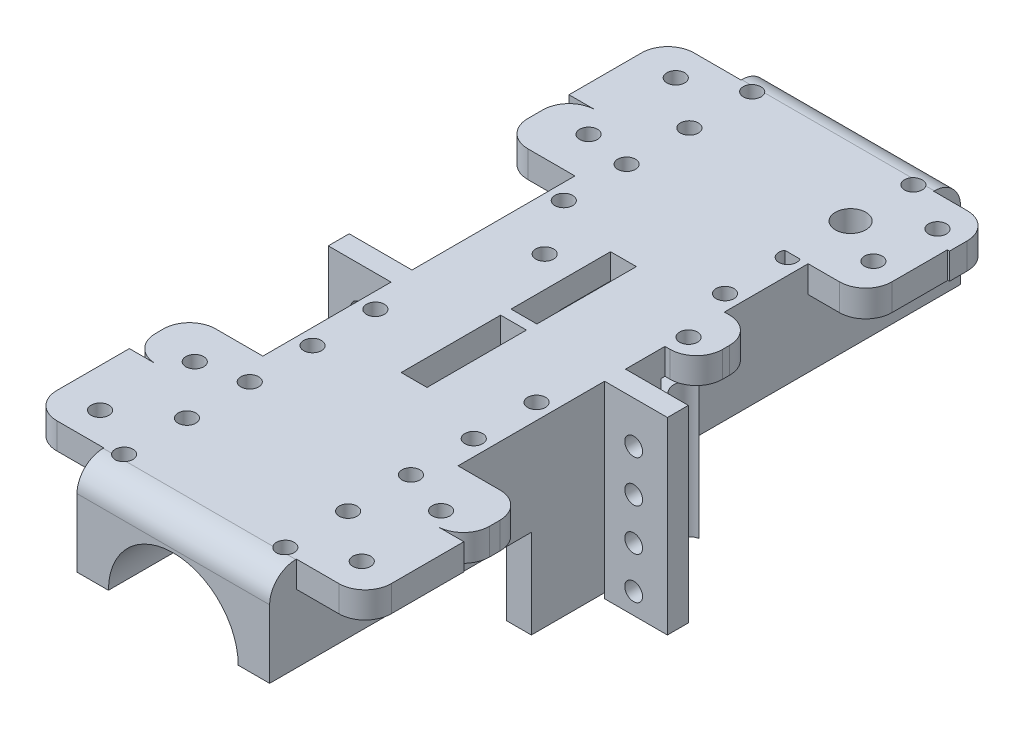
SolidWorks part; units mm, degrees
ref_plane "Plan de face" through (0, 0, 0) normal (0, 0, 1) x (1, 0, 0)
ref_plane "Plan de dessus" through (0, 0, 0) normal (0, 1, 0) x (1, 0, 0)
ref_plane "Plan de droite" through (0, 0, 0) normal (1, 0, 0) x (0, 0, -1)
sketch "Esquisse1" plane through (0, 0, 0) normal (0, 0, 1) x (1, 0, 0)
  line L0 (0, 0) -> (-84.6745, 0) construction
  line L1 (0, 0) -> (94.0931, 0) construction
  line L2 (-12.4, 0) -> (-18.4, 0)
  line L3 (0, 0) -> (0, 12.4) construction
  line L4 (-18.4, 0) -> (-18.4, 18)
  line L5 (-18.4, 18) -> (18.4, 18)
  line L6 (18.4, 0) -> (18.4, 18)
  line L7 (12.4, 0) -> (18.4, 0)
  line L8 (0, 12.4) -> (0, 18) construction
  arc A0 (-12.4, 0) -> (12.4, 0) centre (0, 0) cw
  point P11 (0, 18)
  dimension "D1" = 6
  dimension "D2" = 18
extrude "Boss.-Extru.1" add sketch "Esquisse1" along normal blind 132
sketch "Esquisse3" plane through (0, 18, 0) normal (0, -1, 0) x (1, 0, 0)
  line L0 (-18.4, 66) -> (18.4, 66) construction
  line L3 (0, 66) -> (0, 73.4675) construction
  line L4 (-18.4, 132) -> (-18.4, 0) construction
  line L5 (2.4701, 46) -> (-2.4701, 46)
  line L6 (2.4701, 46) -> (2.4701, 86)
  line L7 (2.4701, 86) -> (-2.4701, 86)
  line L8 (-2.4701, 46) -> (-2.4701, 86)
  line L9 (2.4701, 46) -> (-2.4701, 86) construction
  line L10 (2.4701, 86) -> (-2.4701, 46) construction
  dimension "D1" = 40
extrude "Enlèv. mat.-Extru.2" cut sketch "Esquisse3" along normal blind 9
sketch "Esquisse4" plane through (0, 18, 0) normal (0, 1, 0) x (1, 0, 0)
  line L0 (18.4, -12) -> (-19.7679, -12) construction
  line L1 (0, 0) -> (0, -28.5028) construction
  line L2 (15.4, 0) -> (15.4, -28.5028) construction
  line L3 (18.4, -6) -> (-18.4211, -6) construction
  line L4 (18.4, 0) -> (-18.4, 0) construction
  line L5 (18.4, -132) -> (18.4, 0) construction
  line L6 (18.4, -66) -> (-18.4, -66) construction
  line L7 (-18.4, -132) -> (-18.4, 0) construction
  circle A0 centre (15.4, -6) radius 1.7
  circle A1 centre (15.4, -18) radius 1.7
  circle A2 centre (-15.4, -6) radius 1.7
  circle A3 centre (-15.4, -18) radius 1.7
  circle A4 centre (15.4, -30) radius 1.7
  circle A5 centre (-15.4, -30) radius 1.7
  circle A6 centre (15.4, -42) radius 1.7
  circle A7 centre (-15.4, -42) radius 1.7
  circle A10 centre (-15.4, -126) radius 1.7
  circle A11 centre (-15.4, -114) radius 1.7
  circle A12 centre (-15.4, -102) radius 1.7
  circle A13 centre (-15.4, -90) radius 1.7
  circle A14 centre (-15.4, -78) radius 1.7
  circle A15 centre (15.4, -78) radius 1.7
  circle A16 centre (15.4, -90) radius 1.7
  circle A17 centre (15.4, -102) radius 1.7
  circle A18 centre (15.4, -114) radius 1.7
  circle A19 centre (15.4, -126) radius 1.7
  circle A20 centre (15.4, -54) radius 1.7 [skipped]
  circle A21 centre (-15.4, -54) radius 1.7 [skipped]
  dimension "D1" = 3
  dimension "D2" = 6
  dimension "D3" = 6
  dimension "D4" = 5
extrude "Enlèv. mat.-Extru.3" cut sketch "Esquisse4" against normal blind 18
sketch "Esquisse5" plane through (0, 18, 0) normal (0, 1, 0) x (1, 0, 0)
  line L0 (0, 0) -> (0, -132) construction
  line L1 (18.4, 0) -> (12.4, 0)
  line L2 (18.4, 0) -> (18.4, -24)
  line L3 (18.4, -24) -> (12.4, -24)
  line L4 (12.4, 0) -> (12.4, -24)
  line L5 (18.4, 0) -> (-18.4, 0) construction
  line L6 (18.4, -132) -> (-18.4, -132) construction
  line L7 (18.4, -66) -> (-18.4, -66) construction
  line L8 (18.4, -132) -> (18.4, 0) construction
  line L9 (-18.4, -132) -> (-18.4, 0) construction
  line L10 (-18.4, -132) -> (-12.4, -132)
  line L11 (-12.4, -132) -> (-12.4, -108)
  line L12 (-18.4, -108) -> (-12.4, -108)
  line L13 (-18.4, -132) -> (-18.4, -108)
  line L14 (-18.4, 0) -> (-18.4, -24)
  line L15 (-18.4, -24) -> (-12.4, -24)
  line L16 (-12.4, 0) -> (-12.4, -24)
  line L17 (-18.4, 0) -> (-12.4, 0)
  line L18 (12.4, -132) -> (12.4, -108)
  line L19 (18.4, -108) -> (12.4, -108)
  line L20 (18.4, -132) -> (18.4, -108)
  line L21 (18.4, -132) -> (12.4, -132)
  dimension "D1" = 24
  dimension "D2" = 6
sketch "Esquisse7" plane through (-18.4, 0, 0) normal (-1, 0, 0) x (0, 0, 1)
  line L0 (66, 18) -> (66, 0) construction
  line L1 (132, 18) -> (0, 18) construction
  line L2 (132, 0) -> (0, 0) construction
  line L4 (65, 0) -> (67, 0)
  line L5 (65, 0) -> (65, 18)
  line L6 (65, 18) -> (67, 18)
  line L7 (67, 0) -> (67, 18)
  line L8 (65, 0) -> (67, 18) construction
  line L9 (65, 18) -> (67, 0) construction
  point P6 (66, 9)
  dimension "D1" = 2
extrude "Boss.-Extru.2" add sketch "Esquisse7" against normal through all
sketch "Esquisse8" plane through (0, 0, 65) normal (0, 0, -1) x (-1, 0, 0)
  line L0 (0, 0) -> (16.5032, 0) construction
  line L1 (-12.4, 0) -> (12.4, 0) construction
  line L2 (0, 0) -> (-16.5316, 0) construction
  line L3 (12.775, 0) -> (-12.775, 0)
  arc A0 (12.775, 0) -> (-12.775, 0) centre (0, 0) ccw
extrude "Enlèv. mat.-Extru.5" cut sketch "Esquisse8" along normal blind 15
sketch "Esquisse9" plane through (0, 0, 67) normal (0, 0, 1) x (1, 0, 0)
  line L0 (0, 0) -> (13.8492, 0) construction
  line L1 (12.4, 0) -> (-12.4, 0) construction
  line L2 (0, 0) -> (-14.6616, 0) construction
  line L3 (12.775, 0) -> (-12.775, 0)
  arc A0 (12.775, 0) -> (-12.775, 0) centre (0, 0) ccw
extrude "Enlèv. mat.-Extru.6" cut sketch "Esquisse9" along normal blind 15
sketch "Esquisse10" plane through (0, 0, 0) normal (0, -1, 0) x (1, 0, 0)
  line L0 (12.775, 82) -> (18.4, 82)
  line L1 (18.4, 132) -> (18.4, 0) construction
  line L2 (12.775, 50) -> (18.4, 50)
  line L3 (18.4, 50) -> (18.4, 82)
  line L4 (12.775, 82) -> (12.775, 50)
  line L5 (0, 67) -> (0, 64.9415) construction
  line L6 (12.775, 67) -> (-12.775, 67) construction
  line L7 (-12.775, 50) -> (-18.4, 50)
  line L8 (-18.4, 50) -> (-18.4, 82)
  line L9 (-12.775, 82) -> (-12.775, 50)
  line L10 (-12.775, 82) -> (-18.4, 82)
extrude "Boss.-Extru.3" add sketch "Esquisse10" along normal blind 17
sketch "Esquisse21" plane through (-18.4, 0, 0) normal (-1, 0, 0) x (0, 0, 1)
  line L0 (15.8275, 12.9) -> (113.6873, 12.9) construction
  line L1 (26.5684, 18) -> (120.3195, 18) construction
  line L2 (132, 18) -> (0, 18) construction
  line L3 (26.5684, 18) -> (12.3669, 18) construction
  line L5 (24, 18) -> (36.8707, 18)
  line L6 (24, 18) -> (24, 12.9)
  line L7 (24, 12.9) -> (36.8707, 12.9)
  line L8 (36.8707, 18) -> (36.8707, 12.9)
  line L9 (108, 18) -> (96.4942, 18)
  line L10 (108, 18) -> (108, 12.9)
  line L11 (108, 12.9) -> (96.4942, 12.9)
  line L12 (96.4942, 18) -> (96.4942, 12.9)
  dimension "D1" = 5.1
extrude "Boss.-Extru.7" add sketch "Esquisse21" along normal blind 14
sketch "Esquisse12" plane through (18.4, 0, 0) normal (1, 0, 0) x (0, 0, -1)
  line L1 (-108, 18) -> (-96, 18)
  line L2 (-108, 18) -> (-108, 10)
  line L3 (-108, 10) -> (-96, 10)
  line L4 (-96, 18) -> (-96, 10)
  dimension "D1" = 8
  dimension "D2" = 12
extrude "Boss.-Extru.4" add sketch "Esquisse12" along normal blind 13
sketch "Esquisse14" plane through (18.4, 0, 0) normal (1, 0, 0) x (0, 0, -1)
  line L0 (-96, 18) -> (0, 18) construction
  line L1 (-56.4694, 18) -> (-45.1194, 18)
  line L2 (-56.4694, 18) -> (-56.4694, 10.412)
  line L3 (-56.4694, 10.412) -> (-45.1194, 10.412)
  line L4 (-45.1194, 18) -> (-45.1194, 10.412)
extrude "Boss.-Extru.5" add sketch "Esquisse14" along normal blind 6
sketch "Esquisse16" plane through (24.4, 0, 0) normal (1, 0, 0) x (0, 0, -1)
  line L1 (-43.9372, 13.05) -> (-57.196, 13.05)
  line L2 (-43.9372, 13.05) -> (-43.9372, 8.7778)
  line L3 (-43.9372, 8.7778) -> (-57.196, 8.7778)
  line L4 (-57.196, 13.05) -> (-57.196, 8.7778)
extrude "Enlèv. mat.-Extru.7" cut sketch "Esquisse16" against normal blind 11
sketch "Esquisse17" plane through (18.4, 0, 0) normal (1, 0, 0) x (0, 0, -1)
  line L0 (-45.1194, 18) -> (0, 18) construction
  line L1 (-29.1148, 18) -> (-13.5015, 18)
  line L2 (-29.1148, 18) -> (-29.1148, 12.8991)
  line L3 (-29.1148, 12.8991) -> (-13.5015, 12.8991)
  line L4 (-13.5015, 18) -> (-13.5015, 12.8991)
extrude "Boss.-Extru.6" add sketch "Esquisse17" along normal blind 11 and the other way blind 11
sketch "Esquisse11" plane through (0, 18, 0) normal (0, 1, 0) x (1, 0, 0)
  line L0 (-18.4, -66.6824) -> (18.5601, -66.6824) construction
  line L2 (15.4, -6) -> (15.4, -18) construction
  line L3 (-35.4042, -116.6824) -> (36.1198, -116.6824) construction
  line L4 (-37.228, -16.6824) -> (37.9436, -16.6824) construction
  line L5 (0, -132) -> (0, 0) construction
  line L6 (26.63, -116.6824) -> (26.63, -16.6824) construction
  line L7 (-26.63, -116.6824) -> (-26.63, -16.6824) construction
  line L10 (24.22, -116.6824) -> (24.22, -16.6824) construction
  line L11 (26.63, -102.6824) -> (-26.63, -102.6824) construction
  line L12 (19.13, -116.6824) -> (19.13, -16.6824) construction
  line L13 (-26.63, -52.6824) -> (26.63, -52.6824) construction
  line L14 (26.63, -22.4624) -> (-26.63, -22.4624) construction
  line L15 (-8.37, -116.6824) -> (-8.37, -16.6824) construction
  line L16 (-23.98, -116.6824) -> (-23.98, -16.6824) construction
  line L17 (26.63, -103.9224) -> (-26.63, -103.9224) construction
  line L18 (-26.63, -28.6824) -> (26.63, -28.6824) construction
  circle A0 centre (24.22, -105.0655) radius 1.7
  circle A1 centre (19.13, -52.6824) radius 1.7
  circle A2 centre (24.22, -22.4624) radius 1.7
  circle A3 centre (-8.37, -52.6824) radius 1.7
  circle A4 centre (15.4, -6) radius 1.3
  circle A5 centre (15.4, -18) radius 2.9164
  circle A6 centre (-23.98, -103.9224) radius 1.7
  circle A7 centre (-23.98, -28.6824) radius 1.7
  dimension "D8" = 64
  dimension "D9" = 5.78
  dimension "D10" = 35
  dimension "D11" = 2.65
  dimension "D13" = 12
  dimension "D1" = 50
  dimension "D2" = 50
  dimension "D3" = 26.63
  dimension "D4" = 26.63
  dimension "D5" = 2.41
  dimension "D6" = 14
  dimension "D7" = 7.5
  dimension "D12" = 12.76
extrude "Enlèv. mat.-Extru.8" cut sketch "Esquisse11" against normal blind 8
fillet "Congé1" radius 5 9 edges at (24.4, 15.525, 45.1194) (24.4, 15.525, 56.4694) (31.4, 14, 96) (31.4, 14, 108) (29.4, 15.4496, 29.1148) (-32.4, 15.45, 108) (-32.4, 15.45, 96.4942) (-32.4, 15.45, 36.8707) (-32.4, 15.45, 24)
sketch "Esquisse18" plane through (-2.4701, 0, 0) normal (1, 0, 0) x (0, 0, -1)
  line L1 (-55.739, 13.14) -> (-46.0613, 13.14)
  line L2 (-55.739, 13.14) -> (-55.739, 4.8868)
  line L3 (-55.739, 4.8868) -> (-46.0613, 4.8868)
  line L4 (-46.0613, 13.14) -> (-46.0613, 4.8868)
extrude "Enlèv. mat.-Extru.9" cut sketch "Esquisse18" against normal blind 10
fillet "Congé2" radius 5 2 edges at (0, 18, 0) (0, 18, 132)
sketch "Esquisse19" plane through (18.4, 0, 0) normal (1, 0, 0) x (0, 0, -1)
  line L0 (-24, 12.8991) -> (-139.8858, 12.8991) construction
  line L1 (-24, 12.8991) -> (7.4507, 12.8991) construction
  line L3 (7.4507, 12.8991) -> (-132, 12.8991)
  line L4 (7.4507, 12.8991) -> (7.4507, 5.3045)
  line L5 (7.4507, 5.3045) -> (-132, 5.3045)
  line L6 (-132, 12.8991) -> (-132, 5.3045)
extrude "Enlèv. mat.-Extru.10" cut sketch "Esquisse19" along normal blind 24
sketch "Esquisse20" plane through (0, 0, 0) normal (0, -1, 0) x (1, 0, 0)
  line L0 (0, 67) -> (0, 65) construction
  line L1 (12.775, 67) -> (-12.775, 67) construction
  line L2 (12.775, 65) -> (-12.775, 65) construction
  line L4 (-13.65, 45.9837) -> (13.65, 45.9837)
  line L5 (-13.65, 45.9837) -> (-13.65, 86.0163)
  line L6 (-13.65, 86.0163) -> (13.65, 86.0163)
  line L7 (13.65, 45.9837) -> (13.65, 86.0163)
  line L8 (-13.65, 45.9837) -> (13.65, 86.0163) construction
  line L9 (-13.65, 86.0163) -> (13.65, 45.9837) construction
  point P6 (0, 66)
  dimension "D1" = 27.3
extrude "Enlèv. mat.-Extru.11" cut sketch "Esquisse20" along normal blind 22
sketch "Esquisse22" plane through (0, 13.05, 0) normal (0, -1, 0) x (1, 0, 0)
  circle A0 centre (19.13, 52.6824) radius 2.7804
extrude "Enlèv. mat.-Extru.12" cut sketch "Esquisse22" along normal blind 33
sketch "Esquisse23" plane through (0, 13.14, 0) normal (0, -1, 0) x (1, 0, 0)
  line L0 (-10.9627, 54.7361) -> (-30.5745, 60.2092)
  line L1 (-30.5745, 60.2092) -> (-30.5745, 54.652)
  line L2 (-30.5745, 54.652) -> (-10.9627, 50.3961)
  line L3 (-10.9627, 50.3961) -> (-10.9627, 54.7361)
extrude "Enlèv. mat.-Extru.13" cut sketch "Esquisse23" along normal blind 23
sketch "Esquisse29" plane through (18.4, 0, 0) normal (1, 0, 0) x (0, 0, -1)
  line L0 (-132, 0) -> (0, 0) construction
  line L1 (-96, 18) -> (-56.4694, 18) construction
  line L2 (-68, -18) -> (-64, -18)
  line L3 (-68, -18) -> (-68, 18)
  line L4 (-68, 18) -> (-64, 18)
  line L5 (-64, -18) -> (-64, 18)
  line L6 (-68, -18) -> (-64, 18) construction
  line L7 (-68, 18) -> (-64, -18) construction
  point P4 (-66, 0)
  dimension "D1" = 4
extrude "Boss.-Extru.8" add sketch "Esquisse29" along normal blind 12
sketch "Esquisse30" plane through (-18.4, 0, 0) normal (-1, 0, 0) x (0, 0, 1)
  line L0 (0, 0) -> (132, 0) construction
  line L1 (96.4942, 18) -> (36.8707, 18) construction
  line L2 (68, -18) -> (72, -18)
  line L3 (68, -18) -> (68, 18)
  line L4 (68, 18) -> (72, 18)
  line L5 (72, -18) -> (72, 18)
  line L6 (68, -18) -> (72, 18) construction
  line L7 (68, 18) -> (72, -18) construction
  line L8 (66, 0) -> (66, 18) construction
  line L9 (66, 0) -> (66, -17) construction
  line L10 (82, -17) -> (50, -17) construction
  point P4 (70, 0)
  dimension "D1" = 4
  dimension "D2" = 4
extrude "Boss.-Extru.9" add sketch "Esquisse30" along normal blind 12
sketch "Esquisse31" plane through (0, 0, 68) normal (0, 0, 1) x (1, 0, 0)
  line L0 (23.9549, 18) -> (23.9549, -18) construction
  line L1 (30.4, 18) -> (18.4, 18) construction
  line L2 (30.4, -18) -> (18.4, -18) construction
  circle A0 centre (23.9549, 10) radius 1.7
  circle A1 centre (23.9549, 2) radius 1.7
  circle A2 centre (23.9549, -6) radius 1.7
  circle A3 centre (23.9549, -14) radius 1.7
  dimension "D1" = 8
  dimension "D2" = 4
extrude "Enlèv. mat.-Extru.18" cut sketch "Esquisse31" against normal blind 12
sketch "Esquisse32" plane through (0, 0, 72) normal (0, 0, 1) x (1, 0, 0)
  line L0 (-24.4, 18) -> (-24.4, -18) construction
  line L1 (-30.4, 18) -> (-18.4, 18) construction
  line L2 (-30.4, -18) -> (-18.4, -18) construction
  circle A0 centre (-24.4, 10) radius 1.7
  circle A1 centre (-24.4, 2) radius 1.7
  circle A2 centre (-24.4, -6) radius 1.7
  circle A3 centre (-24.4, -14) radius 1.7
  dimension "D1" = 8
  dimension "D2" = 4
extrude "Enlèv. mat.-Extru.19" cut sketch "Esquisse32" against normal blind 12
sketch "Esquisse34" plane through (0, 18, 0) normal (0, 1, 0) x (1, 0, 0)
  line L1 (-18.4, -108) -> (-32.4, -108)
  line L2 (-18.4, -108) -> (-18.4, -126.8701)
  line L3 (-18.4, -126.8701) -> (-32.4, -126.8701)
  line L4 (-32.4, -108) -> (-32.4, -126.8701)
  line L5 (-18.4, -24) -> (-32.4, -24)
  line L6 (-18.4, -24) -> (-18.4, -5.1276)
  line L7 (-18.4, -5.1276) -> (-32.4, -5.1276)
  line L8 (-32.4, -24) -> (-32.4, -5.1276)
  line L9 (18.4, -108) -> (31.5074, -108)
  line L10 (18.4, -108) -> (18.4, -126.8701)
  line L11 (18.4, -126.8701) -> (31.5074, -126.8701)
  line L12 (31.5074, -108) -> (31.5074, -126.8701)
  line L13 (18.4, -13.5015) -> (29.814, -13.5015)
  line L14 (18.4, -13.5015) -> (18.4, -5.1276)
  line L15 (18.4, -5.1276) -> (29.814, -5.1276)
  line L16 (29.814, -13.5015) -> (29.814, -5.1276)
extrude "Boss.-Extru.10" add sketch "Esquisse34" against normal blind 5
sketch "Esquisse33" plane through (0, 18, 0) normal (0, 1, 0) x (1, 0, 0)
  line L0 (0, -127) -> (0, -5) construction
  line L3 (-26.8114, -121) -> (32.1578, -121) construction
  line L4 (0, -66) -> (-12.764, -66) construction
  line L5 (-18.4, -127) -> (18.4, -127) construction
  line L6 (-14.0252, -127) -> (14.0252, -127) construction
  line L7 (-18.4, -5) -> (18.4, -5) construction
  line L8 (14.0252, -5) -> (-14.0252, -5) construction
  circle A0 centre (-25, -121) radius 1.7
  circle A2 centre (25, -121) radius 1.7
  circle A3 centre (25, -11) radius 1.7
  circle A4 centre (-25, -11) radius 1.7
  dimension "D2" = 25
  dimension "D1" = 55
extrude "Enlèv. mat.-Extru.20" cut sketch "Esquisse33" against normal blind 15
fillet "Congé3" radius 5 4 edges at (-32.4, 15.5, 5.1276) (29.814, 15.5, 5.1276) (-32.4, 15.5, 126.8701) (31.5074, 15.5, 126.8701)
sketch "Esquisse35" plane through (0, 18, 0) normal (0, 1, 0) x (1, 0, 0)
  line L0 (18.4, -126.8701) -> (36.1237, -126.8701) construction
  line L1 (31.5074, -108) -> (31.5074, -129.5345) construction
  line L2 (31.5074, -108) -> (31.5074, -92.746) construction
  line L3 (18.4, -96) -> (34.6627, -96) construction
  line L4 (18.4, -96) -> (-36.8436, -96.5975) construction
  line L5 (-32.4, -108) -> (-32.4, -96.5494) construction
  line L6 (-32.4, -108) -> (-32.4, -132.8506) construction
  line L7 (-18.4, -126.8701) -> (-35.7791, -126.8701) construction
  circle A0 centre (24.22, -105.0655) radius 1.7
  circle A1 centre (25, -121) radius 1.7
  circle A2 centre (-23.98, -103.9224) radius 1.7
  circle A3 centre (-25, -121) radius 1.7
  circle A4 centre (22.52, -108) radius 0.7544
sketch "Esquisse36" plane through (0, 18, 0) normal (0, 1, 0) x (1, 0, 0)
  line L1 (29.814, -5.1276) -> (-32.4, -5.1276)
  line L2 (29.814, -5.1276) -> (29.814, -36.8707)
  line L3 (29.814, -36.8707) -> (-32.4, -36.8707)
  line L4 (-32.4, -5.1276) -> (-32.4, -36.8707)
  circle A0 centre (25, -11) radius 1.6243
  circle A1 centre (24.22, -22.4624) radius 1.7
  circle A2 centre (-25, -11) radius 1.7
  circle A3 centre (-23.98, -28.6824) radius 1.7
  circle A4 centre (21.6371, -20.7624) radius 0.7416
sketch "Esquisse37" plane through (0, 18, 0) normal (0, 1, 0) x (1, 0, 0)
  circle A0 centre (24.22, -105.0655) radius 1.5938
  circle A1 centre (-23.98, -103.9224) radius 1.143
  circle A2 centre (-8.37, -52.6824) radius 1.7305
